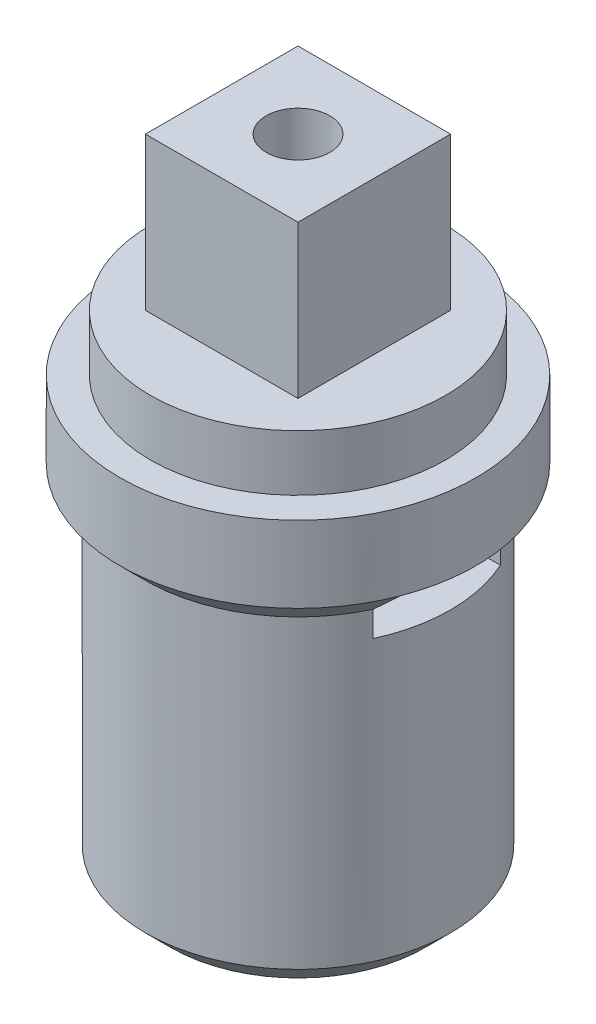
SolidWorks part; units mm, degrees
material "PET"
ref_plane "Спереди" through (0, 0, 0) normal (0, 0, 1) x (1, 0, 0)
ref_plane "Сверху" through (0, 0, 0) normal (0, 1, 0) x (1, 0, 0)
ref_plane "Справа" through (0, 0, 0) normal (1, 0, 0) x (0, 0, -1)
sketch "Эскиз1" plane through (0, 0, 0) normal (0, 1, 0) x (1, 0, 0)
  circle A0 centre (0, 0) radius 6
  dimension "D1" = 12
extrude "Бобышка-Вытянуть1" add sketch "Эскиз1" along normal blind 9
sketch "Эскиз2" plane through (0, 9, 0) normal (0, 1, 0) x (1, 0, 0)
  line L0 (-1.28, 1.4041) -> (-1.28, -1.4041)
  line L1 (1.9, 2.5183) -> (1.9, -3.3812) construction
  arc A0 (-1.28, -1.4041) -> (-1.28, 1.4041) centre (0, 0) ccw
  dimension "D1" = 3.8
  dimension "D2" = 3.18
extrude "Вырез-Вытянуть1" cut sketch "Эскиз2" against normal through all
sketch "Эскиз3" plane through (0, 9, 0) normal (0, 1, 0) x (1, 0, 0)
  circle A0 centre (0, 0) radius 6
extrude "Бобышка-Вытянуть2" add sketch "Эскиз3" along normal blind 3
sketch "Эскиз4" plane through (0, 12, 0) normal (0, 1, 0) x (1, 0, 0)
  circle A0 centre (0, 0) radius 1.5
  dimension "D1" = 3
extrude "Вырез-Вытянуть2" cut sketch "Эскиз4" against normal blind 3
sketch "Эскиз5" plane through (0, 12, 0) normal (0, 1, 0) x (1, 0, 0)
  line L1 (5.4544, 2.5) -> (-5.4544, 2.5)
  line L3 (5.4544, -2.5) -> (-5.4544, -2.5)
  line L5 (8.9983, 2.5) -> (-8.9983, -2.5) construction
  line L6 (8.9983, -2.5) -> (-8.9983, 2.5) construction
  arc A0 (-5.4544, -2.5) -> (5.4544, -2.5) centre (0, 0) ccw
  arc A1 (5.4544, 2.5) -> (-5.4544, 2.5) centre (0, 0) ccw
  point P0 (0, 0)
  dimension "D1" = 5
extrude "Бобышка-Вытянуть3" add sketch "Эскиз5" along normal blind 2
sketch "Эскиз7" plane through (0, 14, 0) normal (0, 1, 0) x (1, 0, 0)
  circle A0 centre (0, 0) radius 7
  dimension "D1" = 14
extrude "Бобышка-Вытянуть4" add sketch "Эскиз7" along normal blind 3
sketch "Эскиз8" plane through (0, 17, 0) normal (0, 1, 0) x (1, 0, 0)
  circle A0 centre (0, 0) radius 5.8
  dimension "D1" = 11.6
extrude "Бобышка-Вытянуть5" add sketch "Эскиз8" along normal blind 2.2
sketch "Эскиз9" plane through (0, 19.2, 0) normal (0, 1, 0) x (1, 0, 0)
  circle A0 centre (0, 0) radius 1.3
  dimension "D1" = 2.6
extrude "Вырез-Вытянуть3" cut sketch "Эскиз9" against normal blind 6
chamfer "Фаска1" distance 1 angle 45 3 edges at (0, 0, 6) (0, 14, 6) (0, 14, -6)
sketch "Эскиз10" plane through (0, 19.2, 0) normal (0, 1, 0) x (1, 0, 0)
  line L1 (-3, 3) -> (3, 3)
  line L2 (-3, 3) -> (-3, -3)
  line L3 (-3, -3) -> (3, -3)
  line L4 (3, 3) -> (3, -3)
  line L5 (-3, 3) -> (3, -3) construction
  line L6 (-3, -3) -> (3, 3) construction
  point P0 (0, 0)
  dimension "D1" = 6
  dimension "D2" = 6
extrude "Бобышка-Вытянуть6" add sketch "Эскиз10" along normal blind 6
sketch "Эскиз11" plane through (0, 25.2, 0) normal (0, 1, 0) x (1, 0, 0)
  circle A0 centre (0, 0) radius 1.25
  dimension "D1" = 2.5
extrude "Вырез-Вытянуть4" cut sketch "Эскиз11" against normal blind 8
